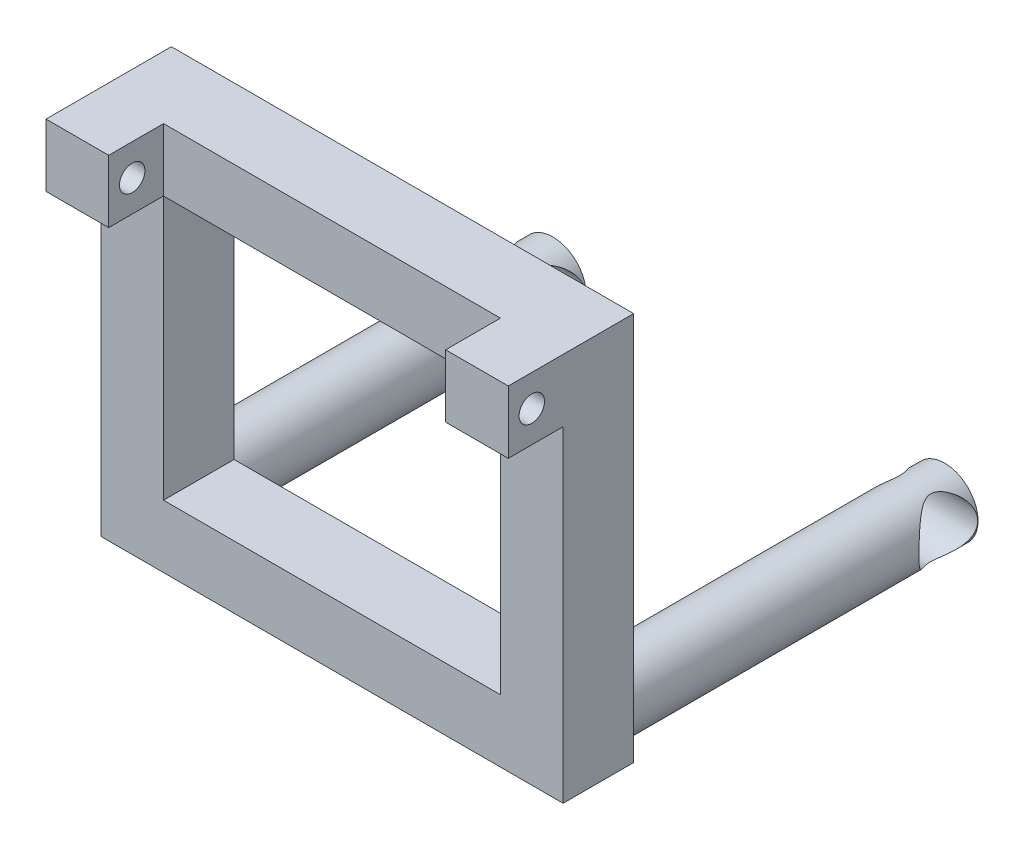
SolidWorks part; units mm, degrees
ref_plane "Front Plane" through (0, 0, 0) normal (0, 0, 1) x (1, 0, 0)
ref_plane "Top Plane" through (0, 0, 0) normal (0, 1, 0) x (1, 0, 0)
ref_plane "Right Plane" through (0, 0, 0) normal (1, 0, 0) x (0, 0, -1)
sketch "Sketch1" plane through (0, 0, 0) normal (0, 0, 1) x (1, 0, 0)
  line L0 (-796.3832, -7.0403) -> (-796.3832, -679.6151)
  line L1 (-956.3832, 152.9597) -> (223.6879, 152.9597)
  line L2 (-956.3832, 152.9597) -> (-956.3832, -839.6151)
  line L3 (-956.3832, -839.6151) -> (223.6879, -839.6151)
  line L4 (223.6879, 152.9597) -> (223.6879, -839.6151)
  line L9 (-796.3832, -679.6151) -> (63.6879, -679.6151)
  line L10 (63.6879, -7.0403) -> (63.6879, -679.6151)
  line L11 (-796.3832, -7.0403) -> (63.6879, -7.0403)
  dimension "D1" = 160
extrude "Boss-Extrude2" add sketch "Sketch1" along normal blind 180
sketch "Sketch2" plane through (0, 0, 180) normal (0, 0, 1) x (1, 0, 0)
  line L1 (-956.3832, 152.9597) -> (-796.3832, 152.9597)
  line L2 (-956.3832, 152.9597) -> (-956.3832, -7.0403)
  line L3 (-956.3832, -7.0403) -> (-796.3832, -7.0403)
  line L4 (-796.3832, 152.9597) -> (-796.3832, -7.0403)
  line L5 (63.6879, -7.0403) -> (223.6879, -7.0403)
  line L6 (63.6879, -7.0403) -> (63.6879, 152.9597)
  line L7 (63.6879, 152.9597) -> (223.6879, 152.9597)
  line L8 (223.6879, -7.0403) -> (223.6879, 152.9597)
extrude "Boss-Extrude3" add sketch "Sketch2" along normal blind 140
sketch "Sketch4" plane through (0, 0, 0) normal (0, 0, -1) x (-1, 0, 0)
  line L0 (956.3832, 152.9597) -> (956.3832, -839.6151) construction
  line L1 (-223.6879, -839.6151) -> (-223.6879, 152.9597) construction
  line L2 (956.3832, -839.6151) -> (-223.6879, -839.6151) construction
  circle A1 centre (-133.6879, -749.6151) radius 85
  circle A2 centre (866.3832, -749.6151) radius 85
  dimension "D1" = 170
  dimension "D4" = 170
  dimension "D5" = 90
  dimension "D2" = 90
  dimension "D3" = 90
  dimension "D6" = 90
extrude "Boss-Extrude4" add sketch "Sketch4" along normal blind 884
ref_plane "Plane1" through (233.6879, 0, 0) normal (1, 0, 0) x (0, 0, -1)
sketch "Sketch5" plane through (233.6879, 0, 0) normal (1, 0, 0) x (0, 0, -1)
  line L1 (0, -834.6151) -> (884, -834.6151) construction
  circle A0 centre (808.3432, -749.6151) radius 75
  dimension "D1" = 150
  dimension "D2" = 85
extrude "Cut-Extrude2" cut sketch "Sketch5" against normal through all
sketch "Sketch6" plane through (223.6879, 0, 0) normal (1, 0, 0) x (0, 0, -1)
  line L0 (-320, -7.0403) -> (-180, -7.0403) construction
  line L2 (-320, -7.0403) -> (-320, 152.9597) construction
  circle A0 centre (-260, 72.9597) radius 32.5
  dimension "D1" = 65
  dimension "D2" = 80
  dimension "D3" = 60
extrude "Cut-Extrude3" cut sketch "Sketch6" against normal through all
